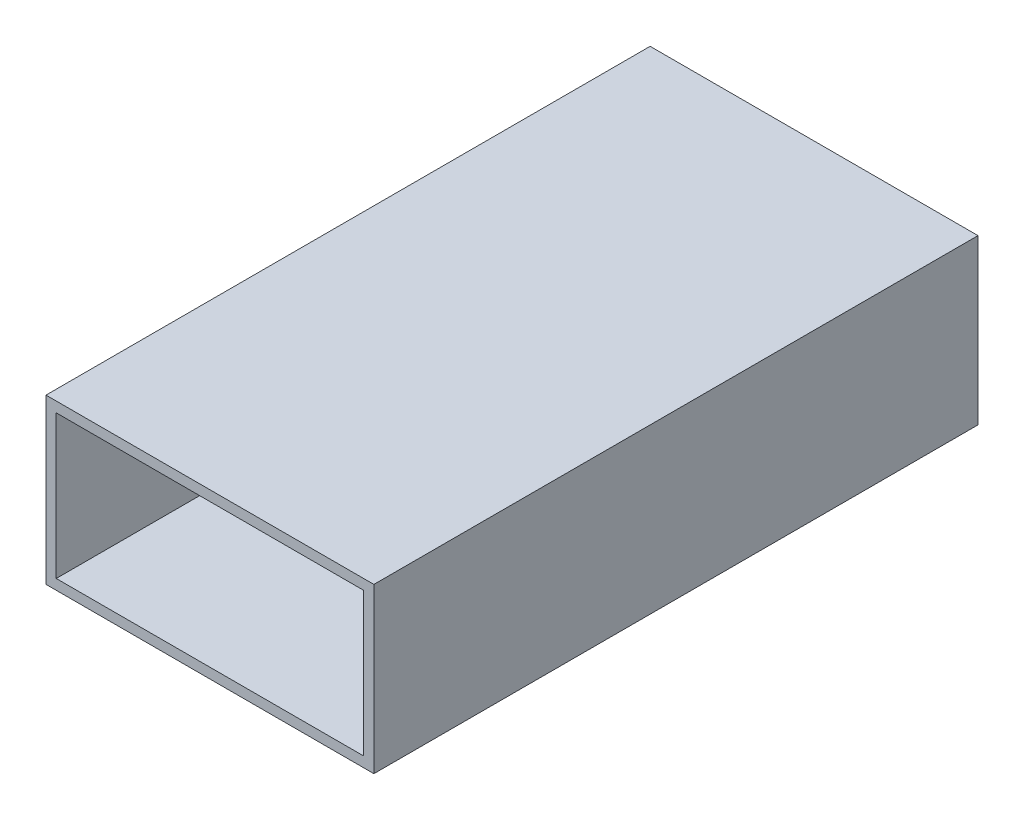
SolidWorks part; units mm, degrees
material "6061-T6 (SS)"
ref_plane "Front Plane" through (0, 0, 0) normal (0, 0, 1) x (1, 0, 0)
ref_plane "Top Plane" through (0, 0, 0) normal (0, 1, 0) x (1, 0, 0)
ref_plane "Right Plane" through (0, 0, 0) normal (1, 0, 0) x (0, 0, -1)
sketch "Sketch1" plane through (0, 0, 0) normal (0, 0, 1) x (1, 0, 0)
  line L1 (-25.4, -12.7) -> (25.4, -12.7)
  line L2 (-25.4, -12.7) -> (-25.4, 12.7)
  line L3 (-25.4, 12.7) -> (25.4, 12.7)
  line L4 (25.4, -12.7) -> (25.4, 12.7)
  line L5 (-25.4, -12.7) -> (25.4, 12.7) construction
  line L6 (-25.4, 12.7) -> (25.4, -12.7) construction
  line L7 (-23.8125, -11.1125) -> (23.8125, -11.1125)
  line L8 (-23.8125, -11.1125) -> (-23.8125, 11.1125)
  line L9 (-23.8125, 11.1125) -> (23.8125, 11.1125)
  line L10 (23.8125, -11.1125) -> (23.8125, 11.1125)
  line L11 (-23.8125, -11.1125) -> (23.8125, 11.1125) construction
  line L12 (-23.8125, 11.1125) -> (23.8125, -11.1125) construction
  point P0 (0, 0)
  point P6 (0, 0)
  dimension "D1" = 50.8
  dimension "D2" = 25.4
  dimension "D3" = 1.5875
  dimension "D4" = 1.5875
extrude "Boss-Extrude1" add sketch "Sketch1" along normal mid plane 93.599
